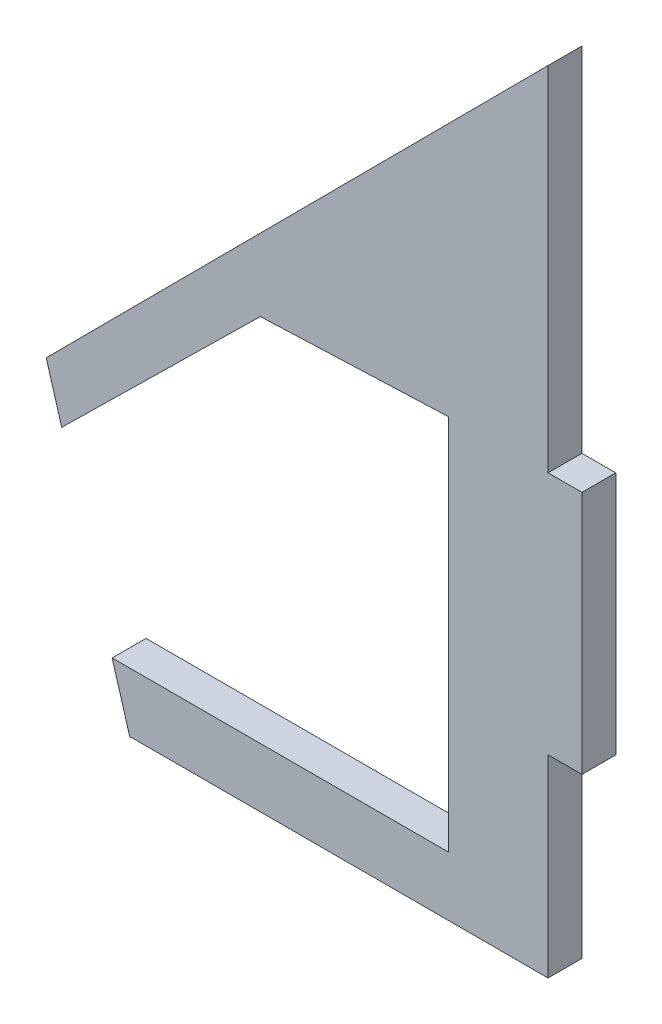
SolidWorks part; units mm, degrees
ref_plane "Front Plane" through (0, 0, 0) normal (0, 0, 1) x (1, 0, 0)
ref_plane "Top Plane" through (0, 0, 0) normal (0, 1, 0) x (1, 0, 0)
ref_plane "Right Plane" through (0, 0, 0) normal (1, 0, 0) x (0, 0, -1)
sketch "Sketch1" plane through (0, 0, 0) normal (0, 0, 1) x (1, 0, 0)
  line L0 (-0.8952, 47.5205) -> (-23.4827, 24.8351)
  line L1 (-0.8952, 31.645) -> (-0.8952, 47.5205)
  line L2 (0.6288, 31.645) -> (-0.8952, 31.645)
  line L3 (-0.8952, 11.9545) -> (-0.8952, 20.6514)
  line L4 (-22.7855, 22.4733) -> (-13.8458, 31.2603)
  line L5 (-13.8458, 31.2603) -> (-5.3767, 31.5935)
  line L6 (-5.3767, 31.5935) -> (-5.3767, 14.6208)
  line L7 (-5.3767, 14.6208) -> (-20.5146, 14.6208)
  line L8 (-22.7855, 22.4733) -> (-23.4827, 24.8351)
  line L9 (-20.5146, 14.6208) -> (-19.7275, 11.9545)
  line L10 (0.6288, 20.6514) -> (-0.8952, 20.6514)
  line L11 (-19.7275, 11.9545) -> (-0.8952, 11.9545)
  line L12 (0.6288, 20.6514) -> (0.6288, 31.645)
  point P6 (0.6288, 10.7921)
  point P11 (0.6288, 47.0154)
extrude "Boss-Extrude1" add sketch "Sketch1" along normal blind 1.524 contours L2 L3 L5 L7 L0 L11 region at (-1.3249, 39.5828, 0)
